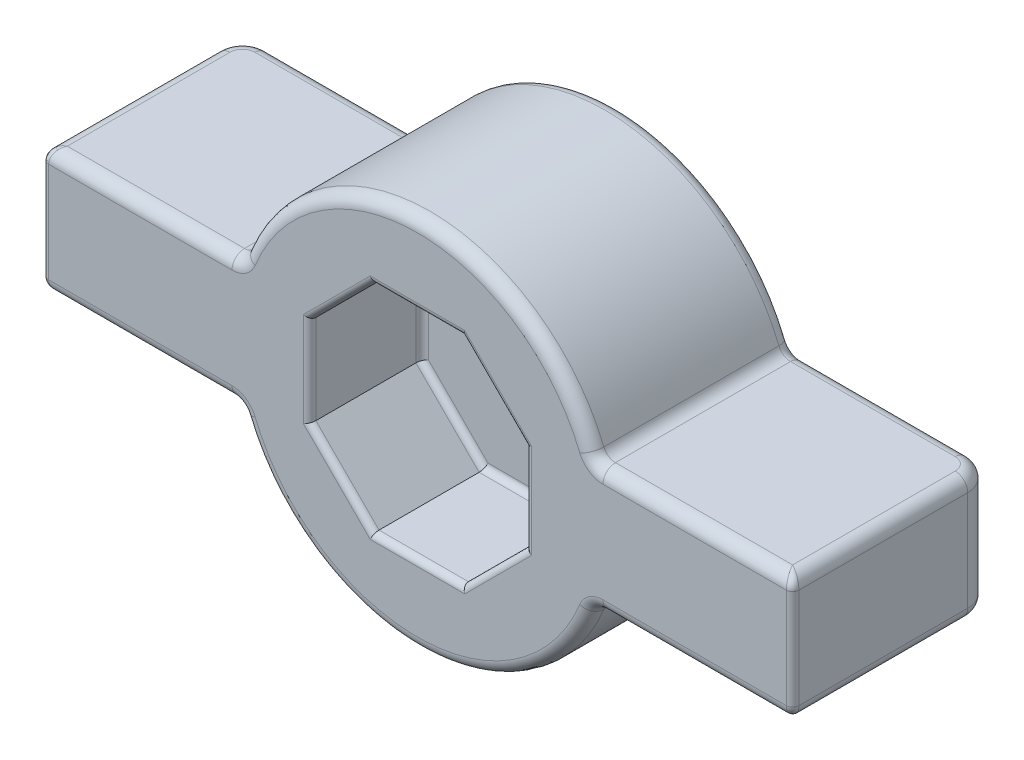
SolidWorks part; units mm, degrees
ref_plane "Front Plane" through (0, 0, 0) normal (0, 0, 1) x (1, 0, 0)
ref_plane "Top Plane" through (0, 0, 0) normal (0, 1, 0) x (1, 0, 0)
ref_plane "Right Plane" through (0, 0, 0) normal (1, 0, 0) x (0, 0, -1)
sketch "Sketch1" plane through (0, 0, 0) normal (0, 0, 1) x (1, 0, 0)
  line L0 (-3.4069, 8.225) -> (0, 8.225)
  line L1 (0, 0) -> (5.5962, 0) construction
  line L2 (-3.4069, 8.225) -> (-8.225, 3.4069)
  line L3 (0, -2.8292) -> (0, -1.4146) construction
  line L4 (-8.225, 3.4069) -> (-8.225, 0)
  line L5 (8.225, 3.4069) -> (3.4069, 8.225)
  line L6 (8.225, 3.4069) -> (8.225, 0)
  line L7 (3.4069, 8.225) -> (0, 8.225)
  line L8 (3.4069, -8.225) -> (8.225, -3.4069)
  line L9 (3.4069, -8.225) -> (0, -8.225)
  line L10 (8.225, -3.4069) -> (8.225, 0)
  line L11 (-8.225, -3.4069) -> (-3.4069, -8.225)
  line L12 (-8.225, -3.4069) -> (-8.225, 0)
  line L13 (-3.4069, -8.225) -> (0, -8.225)
  line L14 (-3.5726, 8.625) -> (0, 8.625)
  line L15 (3.5726, 8.625) -> (0, 8.625)
  line L16 (8.625, 3.5726) -> (3.5726, 8.625)
  line L17 (8.625, 3.5726) -> (8.625, 0)
  line L18 (8.625, -3.5726) -> (8.625, 0)
  line L19 (3.5726, -8.625) -> (8.625, -3.5726)
  line L20 (3.5726, -8.625) -> (0, -8.625)
  line L21 (-3.5726, -8.625) -> (0, -8.625)
  line L22 (-8.625, -3.5726) -> (-3.5726, -8.625)
  line L23 (-8.625, -3.5726) -> (-8.625, 0)
  line L24 (-8.625, 3.5726) -> (-8.625, 0)
  line L25 (-3.5726, 8.625) -> (-8.625, 3.5726)
  circle A0 centre (0, 0) radius 15
  point P24 (0, 0)
  dimension "D1" = 16.45
  dimension "D5" = 30
  dimension "D2" = 16.45
  dimension "D3" = 8.225
  dimension "D4" = 4
extrude "Boss-Extrude1" add sketch "Sketch1" along normal blind 9 contours A0 L25 L14 L15 L16 L17 L18 L19 L20 L21 L22 L23 L24
sketch "Sketch2" plane through (0, 0, 0) normal (0, 0, -1) x (-1, 0, 0)
  circle A1 centre (0, 0) radius 15
  circle A2 centre (0, 0) radius 15
  dimension "D1" = 0
extrude "Boss-Extrude2" add sketch "Sketch2" along normal blind 7
sketch "Sketch3" plane through (0, 0, -7) normal (0, 0, -1) x (-1, 0, 0)
  line L1 (-30, 5) -> (30, 5)
  line L2 (-30, 5) -> (-30, -5)
  line L3 (-30, -5) -> (30, -5)
  line L4 (30, 5) -> (30, -5)
  line L5 (-30, 5) -> (30, -5) construction
  line L6 (-30, -5) -> (30, 5) construction
  circle A0 centre (0, 0) radius 15 construction
  arc A1 (-14.1421, 5) -> (-14.1421, -5) centre (0, 0) ccw
  arc A2 (14.1421, -5) -> (14.1421, 5) centre (0, 0) ccw
  point P0 (0, 0)
  circle M3 centre (0, 0) radius 15
  dimension "D1" = 10
  dimension "D2" = 60
extrude "Boss-Extrude3" add sketch "Sketch3" against normal up to surface (16 mm away) contours L4 L1 L3 M3 | L2 L3 L1 M3 up to face at (0, 0, 9)
fillet "Fillet1" radius 2 2 edges at (-30, 0, -7) (30, 0, -7)
fillet "Fillet2" radius 1 24 edges at (0, 15, -7) (0, -15, 9) (-30, 5, 2) (-22.0711, -5, 9) (-30, -5, 2) (-14.1421, -5, 1) (-14.1421, 5, 1) (-21.0711, 5, -7) (-21.0711, -5, -7) (-22.0711, 5, 9) (0, -15, -7) (0, 15, 9) (22.0711, 5, 9) (22.0711, -5, 9) (14.1421, -5, 1) (14.1421, 5, 1) (30, 5, 2) (30, -5, 2) (-29.4142, -5, -6.4142) (21.0711, 5, -7) (21.0711, -5, -7) (-29.4142, 5, -6.4142) (29.4142, -5, -6.4142) (29.4142, 5, -6.4142)
fillet "Fillet3" radius 0.5 22 edges at (-29.7071, 4.7071, 8.7071) (-29.7071, -4.7071, 8.7071) (29.7071, 4.7071, 8.7071) (29.7071, -4.7071, 8.7071) (-8.625, 0, 0) (-8.625, 0, 9) (-6.0988, -6.0988, 0) (-6.0988, -6.0988, 9) (0, -8.625, 0) (0, -8.625, 9) (6.0988, -6.0988, 0) (6.0988, -6.0988, 9) (8.625, 0, 0) (8.625, 0, 9) (6.0988, 6.0988, 0) (6.0988, 6.0988, 9) (0, 8.625, 0) (0, 8.625, 9) (-6.0988, 6.0988, 0) (-6.0988, 6.0988, 9) (-30, 0, 9) (30, 0, 9)
